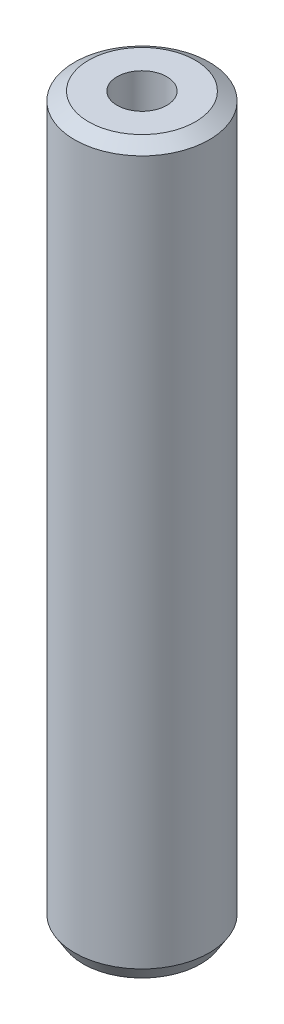
SolidWorks part; units mm, degrees
ref_plane "Front Plane" through (0, 0, 0) normal (0, 0, 1) x (1, 0, 0)
ref_plane "Top Plane" through (0, 0, 0) normal (0, 1, 0) x (1, 0, 0)
ref_plane "Right Plane" through (0, 0, 0) normal (1, 0, 0) x (0, 0, -1)
sketch "Sketch1" plane through (0, 0, 0) normal (0, 1, 0) x (1, 0, 0)
  circle A0 centre (0, 0) radius 12.5
  dimension "SHAFT_OD" = 25
extrude "Boss-Extrude1" add sketch "Sketch1" along normal blind 134.9408
sketch "Sketch2" plane through (0, 0, 0) normal (0, 1, 0) x (1, 0, 0)
  circle A0 centre (0, 0) radius 4.6171
  dimension "BORE_D" = 9.2342
extrude "Cut-Extrude1" cut sketch "Sketch2" along normal through all
chamfer "Chamfer1" distance 1.5975 angle 58.299 2 edges at (0, 134.9408, 12.5) (0, 0, 12.5) first distance on face at (0, 134.9408, 12.5) first distance on face at (0, 0, 4.6171)
